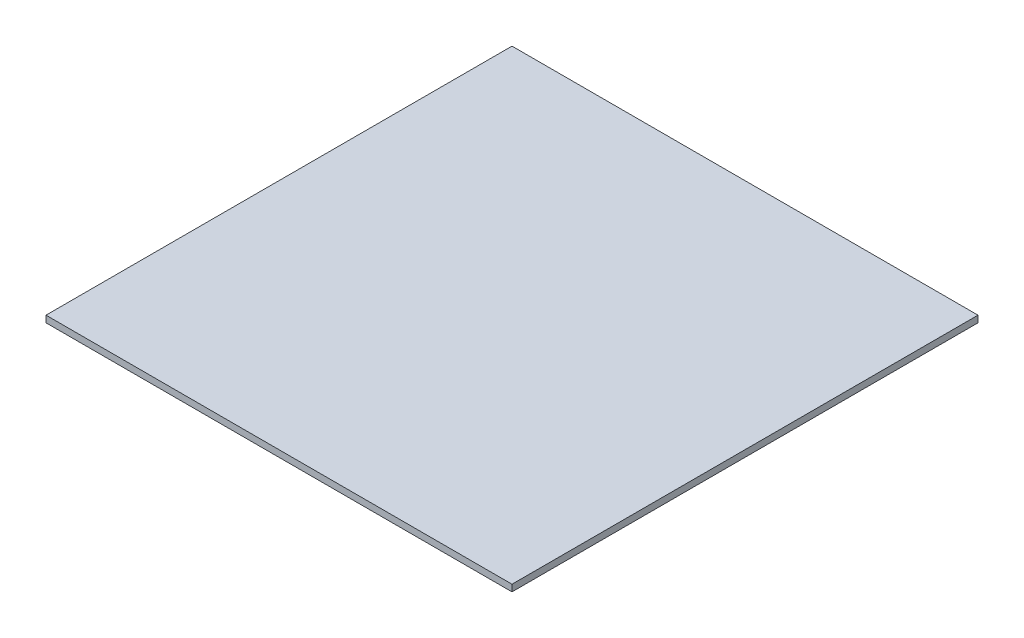
SolidWorks part; units mm, degrees
ref_plane "Front Plane" through (0, 0, 0) normal (0, 0, 1) x (1, 0, 0)
ref_plane "Top Plane" through (0, 0, 0) normal (0, 1, 0) x (1, 0, 0)
ref_plane "Right Plane" through (0, 0, 0) normal (1, 0, 0) x (0, 0, -1)
sketch "Sketch1" plane through (0, 0, 0) normal (0, 1, 0) x (1, 0, 0)
  line L1 (-36.4347, 237.0017) -> (243.5653, 237.0017)
  line L2 (-36.4347, 237.0017) -> (-36.4347, -42.9983)
  line L3 (-36.4347, -42.9983) -> (243.5653, -42.9983)
  line L4 (243.5653, 237.0017) -> (243.5653, -42.9983)
extrude "Boss-Extrude1" add sketch "Sketch1" along normal blind 4
